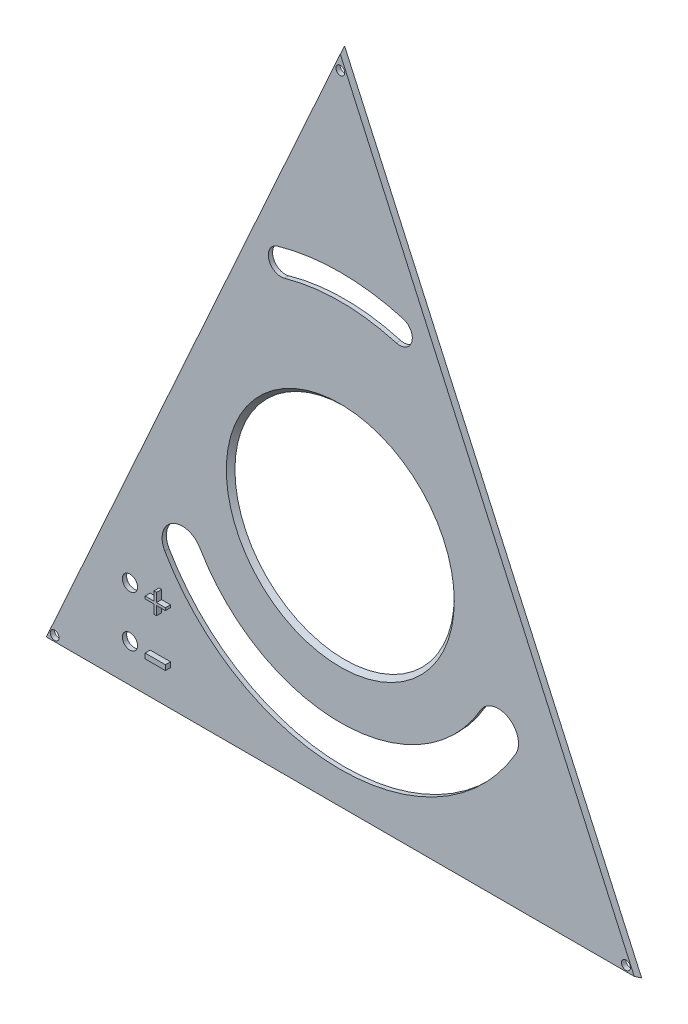
SolidWorks part; units mm, degrees
ref_plane "Front Plane" through (0, 0, 0) normal (0, 0, 1) x (1, 0, 0)
ref_plane "Top Plane" through (0, 0, 0) normal (0, 1, 0) x (1, 0, 0)
ref_plane "Right Plane" through (0, 0, 0) normal (1, 0, 0) x (0, 0, -1)
sketch "Sketch1" plane through (0, 0, 0) normal (0, 0, 1) x (1, 0, 0)
  line L3 (117.2747, -93.5235) -> (0, 166.4874)
  line L4 (0, 166.4874) -> (-117.2747, -93.5235)
  line L5 (-117.2747, -93.5235) -> (117.2747, -93.5235)
  line L6 (117.2747, -93.5235) -> (0, 166.4874)
  line L7 (0, 166.4874) -> (-117.2747, -93.5235)
  line L8 (-117.2747, -93.5235) -> (117.2747, -93.5235)
  dimension "D1" = 0
extrude "Boss-Extrude1" add sketch "Sketch1" along normal blind 1.7 draft 25
sketch "Sketch2" plane through (0, 0, 1.7) normal (0, 0, 1) x (1, 0, 0)
  circle A1 centre (0, 0) radius 40
  dimension "D1" = 80
extrude "Cut-Extrude1" cut sketch "Sketch2" against normal through all
sketch "Sketch3" plane through (0, 0, 1.7) normal (0, 0, 1) x (1, 0, 0)
  circle A0 centre (0, 158.9874) radius 1.75 construction
  circle A1 centre (112.7747, -90.5235) radius 1.75 construction
  circle A2 centre (-112.7747, -90.5235) radius 1.75 construction
  circle A3 centre (0, 158.9874) radius 1.75
  circle A4 centre (112.7747, -90.5235) radius 1.75
  circle A5 centre (-112.7747, -90.5235) radius 1.75
extrude "Cut-Extrude2" cut sketch "Sketch3" against normal through all
chamfer "Chamfer1" distance 5 angle 45 1 edges at (40, 0, 1.7)
sketch "Sketch4" plane through (0, 0, 1.7) normal (0, 0, 1) x (1, 0, 0)
  line L0 (0, 0) -> (0, -116.0202) construction
  line L1 (0, 0) -> (114.838, -66.3017) construction
  line L2 (0, 0) -> (-148.9388, -85.9899) construction
  line L3 (0, 0) -> (0, 188.692) construction
  line L4 (0, 0) -> (-45.0277, 157.0301) construction
  line L5 (0, 0) -> (55.1805, 192.4372) construction
  arc A0 (69.282, -40) -> (-69.282, -40) centre (0, 0) cw
  arc A1 (55.4256, -32) -> (-55.4256, -32) centre (0, 0) cw
  arc A2 (-69.282, -40) -> (-55.4256, -32) centre (-62.3538, -36) cw
  arc A3 (55.4256, -32) -> (69.282, -40) centre (62.3538, -36) cw
  circle A4 centre (-83.0475, -57.7307) radius 3
  circle A5 centre (-83.0475, -77.7307) radius 3
  arc A6 (-24.8074, 86.5136) -> (24.8074, 86.5136) centre (0, 0) cw
  arc A7 (-22.051, 76.9009) -> (22.051, 76.9009) centre (0, 0) cw
  arc A8 (24.8074, 86.5136) -> (22.051, 76.9009) centre (23.4292, 81.7072) cw
  arc A9 (-24.8074, 86.5136) -> (-22.051, 76.9009) centre (-23.4292, 81.7072) ccw
  dimension "D3" = 80
  dimension "D4" = 16
  dimension "D5" = 6
  dimension "D11" = 90
  dimension "D1" = 60
  dimension "D2" = 60
  dimension "D6" = 20
  dimension "D7" = 33
  dimension "D8" = 15
  dimension "D9" = 16
  dimension "D10" = 16
  dimension "D12" = 10
extrude "Cut-Extrude4" cut sketch "Sketch4" against normal up to next
sketch "Sketch6" plane through (0, 0, 1.7) normal (0, 0, 1) x (1, 0, 0)
  line L0 (-86.0475, -57.7307) -> (-80.0475, -57.7307) construction
  line L1 (-71.5475, -53.7307) -> (-70.5475, -53.7307)
  line L2 (-71.5475, -53.7307) -> (-71.5475, -57.2307)
  line L3 (-71.5475, -61.7307) -> (-70.5475, -61.7307)
  line L4 (-70.5475, -53.7307) -> (-70.5475, -57.2307)
  line L5 (-71.5475, -53.7307) -> (-70.5475, -61.7307) construction
  line L6 (-71.5475, -61.7307) -> (-70.5475, -53.7307) construction
  line L7 (-75.0475, -57.2307) -> (-71.5475, -57.2307)
  line L8 (-75.0475, -57.2307) -> (-75.0475, -58.2307)
  line L9 (-75.0475, -58.2307) -> (-71.5475, -58.2307)
  line L10 (-67.0475, -57.2307) -> (-67.0475, -58.2307)
  line L11 (-75.0475, -57.2307) -> (-67.0475, -58.2307) construction
  line L12 (-75.0475, -58.2307) -> (-67.0475, -57.2307) construction
  line L13 (-83.0475, -60.7307) -> (-83.0475, -54.7307) construction
  line L14 (-80.0475, -57.7307) -> (-65.3893, -57.7307) construction
  line L15 (-71.5475, -58.2307) -> (-71.5475, -61.7307)
  line L16 (-70.5475, -58.2307) -> (-67.0475, -58.2307)
  line L17 (-70.5475, -57.2307) -> (-67.0475, -57.2307)
  line L18 (-70.5475, -58.2307) -> (-70.5475, -61.7307)
  line L19 (-86.0475, -77.7307) -> (-69.7862, -77.7307) construction
  line L21 (-75.0475, -76.7307) -> (-67.0475, -76.7307)
  line L22 (-75.0475, -76.7307) -> (-75.0475, -78.7307)
  line L23 (-75.0475, -78.7307) -> (-67.0475, -78.7307)
  line L24 (-67.0475, -76.7307) -> (-67.0475, -78.7307)
  line L25 (-75.0475, -76.7307) -> (-67.0475, -78.7307) construction
  line L26 (-75.0475, -78.7307) -> (-67.0475, -76.7307) construction
  circle A0 centre (-83.0475, -57.7307) radius 3 construction
  circle A1 centre (-83.0475, -77.7307) radius 3 construction
  point P0 (-71.0475, -57.7307)
  point P5 (-71.0475, -57.7307)
  point P14 (-71.0475, -77.7307)
  dimension "D1" = 1
  dimension "D2" = 12
  dimension "D3" = 8
  dimension "D4" = 8
  dimension "D5" = 2
  dimension "D6" = 8
extrude "Boss-Extrude2" add sketch "Sketch6" along normal blind 2
